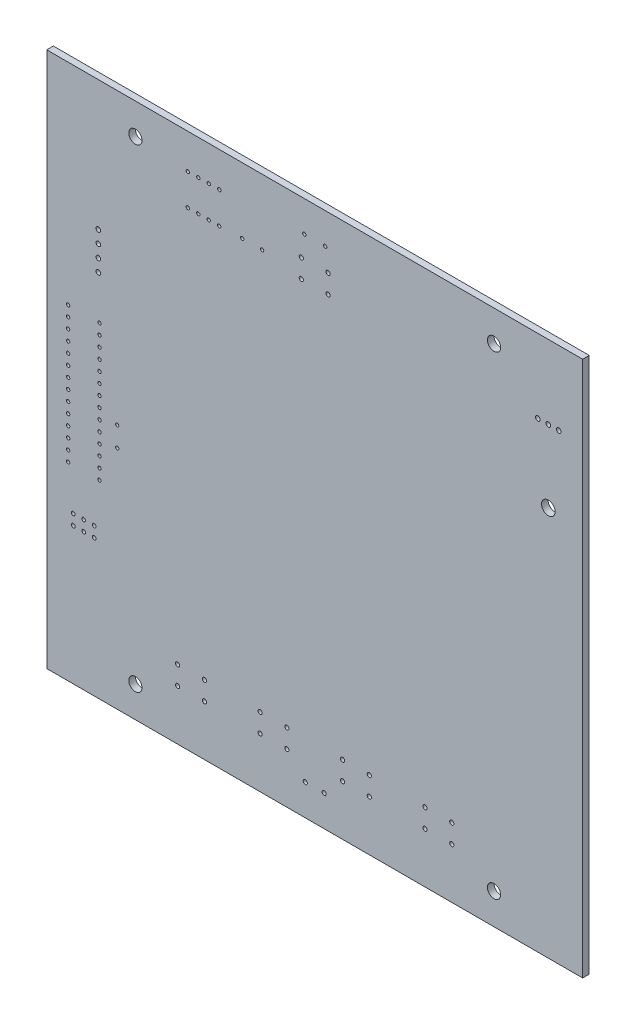
SolidWorks part; units mm, degrees
ref_plane "Ebene vorne" through (0, 0, 0) normal (0, 0, 1) x (1, 0, 0)
ref_plane "Ebene oben" through (0, 0, 0) normal (0, 1, 0) x (1, 0, 0)
ref_plane "Ebene rechts" through (0, 0, 0) normal (1, 0, 0) x (0, 0, -1)
ref_plane "Dielectric_Layer Layer 1" through (0, 0, 1.6) normal (0, 0, 1) x (1, 0, 0)
sketch "Skizze1" plane through (0, 0, 0) normal (0, 0, 1) x (1, 0, 0)
  line L0 (2.5, 2.5) -> (2.5, 132.5)
  line L1 (2.5, 132.5) -> (132.5, 132.5)
  line L2 (132.5, 132.5) -> (132.5, 2.5)
  line L3 (132.5, 2.5) -> (2.5, 2.5)
extrude "Board_Outline" add sketch "Skizze1" along normal blind 1.6 separate body
sketch "Skizze2" plane through (0, 0, 0) normal (0, 0, 1) x (1, 0, 0)
  circle A0 centre (24, 125) radius 1.6
  circle A1 centre (111, 10) radius 1.6
  circle A2 centre (24, 10) radius 1.6
  circle A3 centre (111, 125) radius 1.6
  circle A4 centre (124.17, 97.094) radius 1.651
extrude "NPTH" cut sketch "Skizze2" along normal through all
sketch "Skizze3" plane through (0, 0, 0) normal (0, 0, 1) x (1, 0, 0)
  circle A0 centre (15.31, 81.51) radius 0.405
  circle A1 centre (15.31, 78.97) radius 0.405
  circle A2 centre (15.31, 76.43) radius 0.405
  circle A3 centre (15.31, 73.89) radius 0.405
  circle A4 centre (15.31, 71.35) radius 0.405
  circle A5 centre (15.31, 68.81) radius 0.405
  circle A6 centre (15.31, 66.27) radius 0.405
  circle A7 centre (15.31, 63.73) radius 0.405
  circle A8 centre (15.31, 61.19) radius 0.405
  circle A9 centre (15.31, 58.65) radius 0.405
  circle A10 centre (15.31, 56.11) radius 0.405
  circle A11 centre (15.31, 53.57) radius 0.405
  circle A12 centre (15.31, 51.03) radius 0.405
  circle A13 centre (15.31, 48.49) radius 0.405
  circle A14 centre (7.69, 48.49) radius 0.405
  circle A15 centre (7.69, 51.03) radius 0.405
  circle A16 centre (7.69, 53.57) radius 0.405
  circle A17 centre (7.69, 56.11) radius 0.405
  circle A18 centre (7.69, 58.65) radius 0.405
  circle A19 centre (7.69, 61.19) radius 0.405
  circle A20 centre (7.69, 63.73) radius 0.405
  circle A21 centre (7.69, 66.27) radius 0.405
  circle A22 centre (7.69, 68.81) radius 0.405
  circle A23 centre (7.69, 71.35) radius 0.405
  circle A24 centre (7.69, 73.89) radius 0.405
  circle A25 centre (7.69, 76.43) radius 0.405
  circle A26 centre (7.69, 78.97) radius 0.405
  circle A27 centre (7.69, 81.51) radius 0.405
  circle A28 centre (64.96, 125) radius 0.405
  circle A29 centre (70.04, 125) radius 0.405
  circle A30 centre (15.01, 92) radius 0.56
  circle A31 centre (15, 101) radius 0.56
  circle A32 centre (15.02, 95) radius 0.56
  circle A33 centre (15.01, 98.01) radius 0.56
  circle A34 centre (19.59, 62.2) radius 0.405
  circle A35 centre (19.59, 57.38) radius 0.405
  circle A36 centre (121.63, 114.62) radius 0.56
  circle A37 centre (124.17, 114.62) radius 0.56
  circle A38 centre (126.71, 114.62) radius 0.56
  circle A39 centre (54.74, 116.59) radius 0.405
  circle A40 centre (49.92, 116.59) radius 0.405
  circle A41 centre (44.34, 116.42) radius 0.405
  circle A42 centre (41.8, 116.42) radius 0.405
  circle A43 centre (39.26, 116.42) radius 0.405
  circle A44 centre (36.72, 116.42) radius 0.405
  circle A45 centre (36.72, 124.04) radius 0.405
  circle A46 centre (39.26, 124.04) radius 0.405
  circle A47 centre (41.8, 124.04) radius 0.405
  circle A48 centre (44.34, 124.04) radius 0.405
  circle A49 centre (70.75, 119.76) radius 0.51
  circle A50 centre (64.25, 119.76) radius 0.51
  circle A51 centre (70.75, 115.24) radius 0.51
  circle A52 centre (64.25, 115.24) radius 0.51
  circle A53 centre (34.25, 14.74) radius 0.51
  circle A54 centre (40.75, 14.74) radius 0.51
  circle A55 centre (34.25, 19.26) radius 0.51
  circle A56 centre (40.75, 19.26) radius 0.51
  circle A57 centre (54.25, 14.74) radius 0.51
  circle A58 centre (60.75, 14.74) radius 0.51
  circle A59 centre (54.25, 19.26) radius 0.51
  circle A60 centre (60.75, 19.26) radius 0.51
  circle A61 centre (74.25, 14.74) radius 0.51
  circle A62 centre (80.75, 14.74) radius 0.51
  circle A63 centre (74.25, 19.26) radius 0.51
  circle A64 centre (80.75, 19.26) radius 0.51
  circle A65 centre (94.25, 14.74) radius 0.51
  circle A66 centre (100.75, 14.74) radius 0.51
  circle A67 centre (94.25, 19.26) radius 0.51
  circle A68 centre (100.75, 19.26) radius 0.51
  circle A69 centre (65.21, 10) radius 0.51
  circle A70 centre (69.79, 10) radius 0.51
  circle A71 centre (8.92, 38.29) radius 0.455
  circle A72 centre (8.92, 35.75) radius 0.455
  circle A73 centre (11.46, 38.29) radius 0.455
  circle A74 centre (11.46, 35.75) radius 0.455
  circle A75 centre (14, 38.29) radius 0.455
  circle A76 centre (14, 35.75) radius 0.455
extrude "PTH" cut sketch "Skizze3" along normal through all
